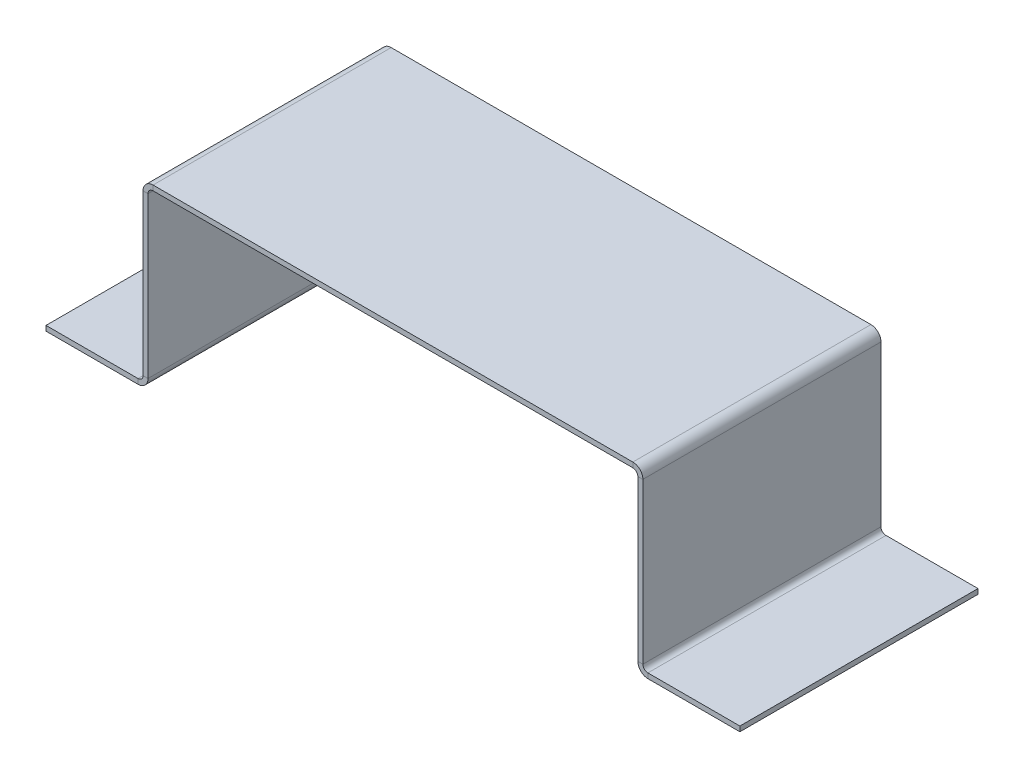
SolidWorks part; units mm, degrees
note: The reader was unsure of these and kept them because the rebuilt part matched: flange length of "Edge-Flange1", "Edge-Flange2".
ref_plane "Front Plane" through (0, 0, 0) normal (0, 0, 1) x (1, 0, 0)
ref_plane "Top Plane" through (0, 0, 0) normal (0, 1, 0) x (1, 0, 0)
ref_plane "Right Plane" through (0, 0, 0) normal (1, 0, 0) x (0, 0, -1)
sketch "Sketch1" plane through (0, 0, 0) normal (0, 1, 0) x (1, 0, 0)
  line L1 (-36, -17.5) -> (36, -17.5)
  line L2 (-36, -17.5) -> (-36, 17.5)
  line L3 (-36, 17.5) -> (36, 17.5)
  line L4 (36, -17.5) -> (36, 17.5)
  line L5 (-36, -17.5) -> (36, 17.5) construction
  line L6 (-36, 17.5) -> (36, -17.5) construction
  point P0 (0, 0)
  dimension "D1" = 72
  dimension "D2" = 35
base flange "Base-Flange1" sketch "Sketch1" thickness 0.7366 reverse thickness direction no parameters "D1"=0.7366
edge flange "Edge-Flange1" sketch "Sketch10" flange profiles "Sketch10", "Sketch11" flange angle 90 flange length 25.7366 flange position material outside bend radius 0.7366 thickness 0.7366 relief rectangular parameters "D6"=10, "D8"=1
sketch "Sketch10" plane through (36, -0.7366, 0) normal (1, 0, 0) x (0, 0, 1)
  line L0 (17.5, 0) -> (-17.5, 0) construction
  line L1 (17.5, 0) -> (-17.5, 0)
  line L2 (-17.5, 0) -> (-17.5, 25)
  line L3 (-17.5, 25) -> (17.5, 25)
  line L4 (17.5, 25) -> (17.5, 0)
  dimension "D1" = 25
sketch "Sketch11" plane through (-36, -0.7366, 0) normal (-1, 0, 0) x (0, 0, -1)
  line L0 (17.5, 0) -> (-17.5, 0) construction
  line L1 (17.5, 0) -> (-17.5, 0)
  line L2 (-17.5, 0) -> (-17.5, 25)
  line L3 (-17.5, 25) -> (17.5, 25)
  line L4 (17.5, 25) -> (17.5, 0)
bend "EdgeBend1" bend radius 0.7366 bend angle 90 parameters "D5"=1
bend "EdgeBend2" bend radius 0.7366 bend angle 90 parameters "D5"=2
edge flange "Edge-Flange2" sketch "Sketch16" flange profiles "Sketch16", "Sketch17" flange angle 90 flange length 15 flange position material outside bend radius 0.7366 thickness 0.7366 relief rectangular parameters "D6"=10, "D8"=1
sketch "Sketch16" plane through (-36.7366, -25.7366, 0) normal (0, -1, 0) x (0, 0, 1)
  line L0 (-17.5, 0) -> (17.5, 0) construction
  line L1 (-17.5, 0) -> (17.5, 0)
  line L2 (-17.5, 0) -> (-17.5, 14.2634)
  line L3 (-17.5, 14.2634) -> (17.5, 14.2634)
  line L4 (17.5, 14.2634) -> (17.5, 0)
sketch "Sketch17" plane through (36.7366, -25.7366, 0) normal (0, -1, 0) x (0, 0, -1)
  line L0 (-17.5, 0) -> (17.5, 0) construction
  line L1 (-17.5, 0) -> (17.5, 0)
  line L2 (-17.5, 0) -> (-17.5, 14.2634)
  line L3 (-17.5, 14.2634) -> (17.5, 14.2634)
  line L4 (17.5, 14.2634) -> (17.5, 0)
bend "EdgeBend3" bend radius 0.7366 bend angle 90 parameters "D5"=3
bend "EdgeBend4" bend radius 0.7366 bend angle 90 parameters "D5"=4
sketch "Bend-Lines1" plane through (0, 0, 0) normal (0, 1, 0) x (1, 0, 0)
sketch "Bounding-Box1" plane through (0, 0, 0) normal (0, 1, 0) x (1, 0, 0)
sheet metal parameters "Sheet-Metal1" thickness 0.7366 parameters "D1"=0.7366
flat pattern "Flat-Pattern1" [suppressed]
sketch "Bend-Lines2" plane through (0, 0, 0) normal (0, 1, 0) x (1, 0, 0)
sketch "Bounding-Box2" [suppressed] plane through (0, 0, 0) normal (0, 1, 0) x (1, 0, 0)
sheet metal parameters "Sheet-Metal2" thickness 0.7366 parameters "D1"=0.7366
flat pattern "Flat-Pattern1" [suppressed]
sketch "Bend-Lines2" plane through (0, 0, 0) normal (0, 1, 0) x (1, 0, 0)
sketch "Bounding-Box2" [suppressed] plane through (0, 0, 0) normal (0, 1, 0) x (1, 0, 0)
bend of the flat pattern "Flatten-<EdgeBend1>1"
bend of the flat pattern "Flatten-<EdgeBend2>1"
sheet metal parameters "Sheet-Metal3" thickness 0.7366 parameters "D1"=0.7366
flat pattern "Flat-Pattern1" [suppressed]
sketch "Bend-Lines2" plane through (0, 0, 0) normal (0, 1, 0) x (1, 0, 0)
sketch "Bounding-Box2" [suppressed] plane through (0, 0, 0) normal (0, 1, 0) x (1, 0, 0)
bend of the flat pattern "Flatten-<EdgeBend1>1"
bend of the flat pattern "Flatten-<EdgeBend2>1"
bend of the flat pattern "Flatten-<EdgeBend3>1"
bend of the flat pattern "Flatten-<EdgeBend4>1"
